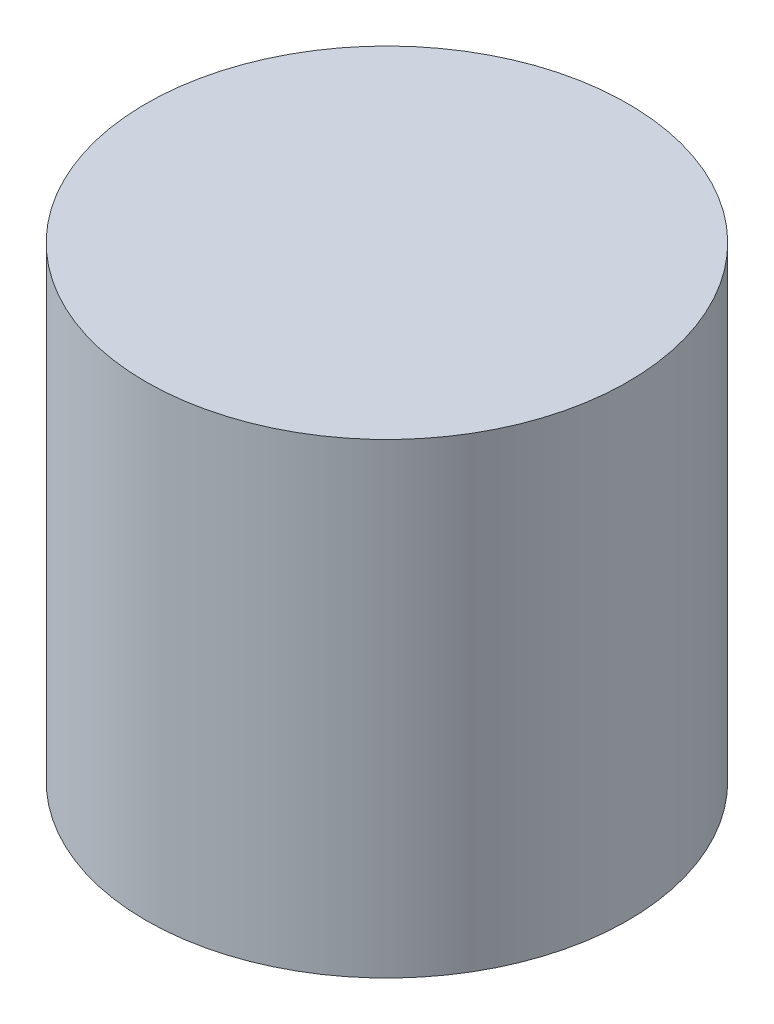
SolidWorks part; units mm, degrees
ref_plane "Front Plane" through (0, 0, 0) normal (0, 0, 1) x (1, 0, 0)
ref_plane "Top Plane" through (0, 0, 0) normal (0, 1, 0) x (1, 0, 0)
ref_plane "Right Plane" through (0, 0, 0) normal (1, 0, 0) x (0, 0, -1)
sketch "Sketch1" plane through (0, 0, 0) normal (0, 1, 0) x (1, 0, 0)
  circle A0 centre (0, 0) radius 3.1
  circle A1 centre (0, 0) radius 1.975
  dimension "D1" = 6.2
  dimension "D2" = 3.95
extrude "Boss-Extrude1" add sketch "Sketch1" along normal blind 6 contours A1 | A0 A1 region at (-3.0123, 0, 0) region at (0, 0, 0)
extrude "Cut-Extrude1" cut sketch "Sketch1<4>" along normal offset from surface (4 mm away) 2 contours A1 region at (0, 0, 0) up to face at (0, 6, 3.1)
sketch "Sketch1<4>" plane through (0, 0, 0) normal (0, 1, 0) x (1, 0, 0) same geometry as "Sketch1"
